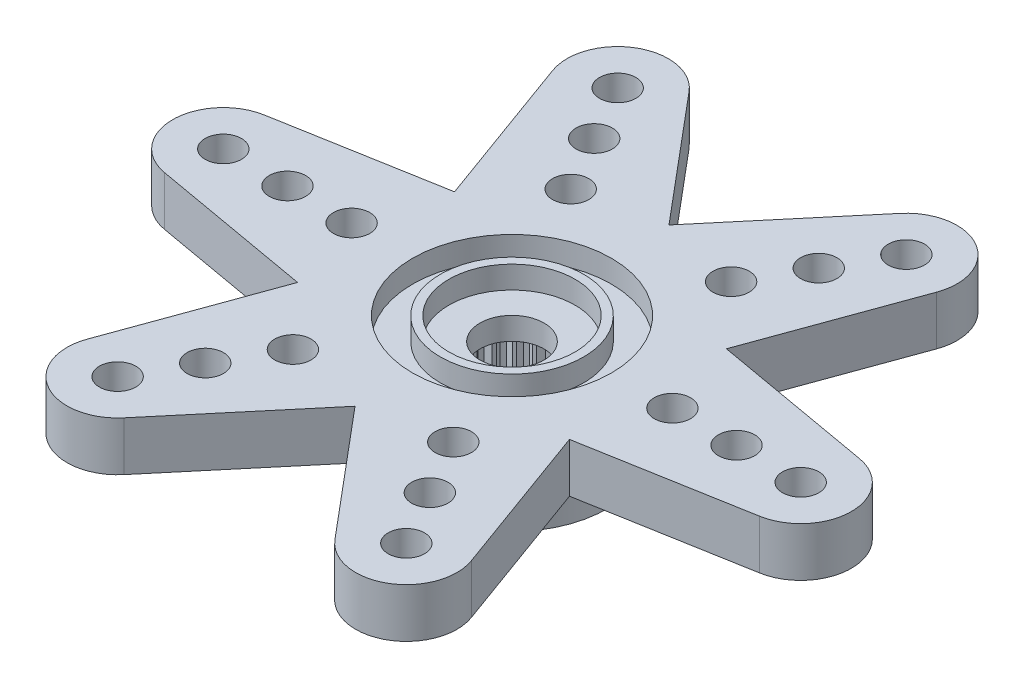
SolidWorks part; units mm, degrees
material "PA Type 6"
ref_plane "Plan de face" through (0, 0, 0) normal (0, 0, 1) x (1, 0, 0)
ref_plane "Plan de dessus" through (0, 0, 0) normal (0, 1, 0) x (1, 0, 0)
ref_plane "Plan de droite" through (0, 0, 0) normal (1, 0, 0) x (0, 0, -1)
ref_axis "Axe1" through (0, 0, 0) along (0, 1, 0)
sketch "Esquisse1" plane through (0, 0, 0) normal (0, 1, 0) x (1, 0, 0)
  line L0 (-15.87, 0) -> (15.87, 0) construction
  line L1 (0, 0) -> (0, -8.9896) construction
  line L4 (0, 0) -> (-6.3566, 3.67) construction
  line L11 (-13.9127, 2.3338) -> (-6.3566, 3.67)
  line L12 (-13.9127, -2.3338) -> (-6.3566, -3.67)
  line L13 (-6.3566, 3.67) -> (0, 3.67)
  line L14 (-6.3566, -3.67) -> (0, -3.67)
  circle A0 centre (0, 0) radius 15.87 construction
  arc A1 (-13.9127, 2.3338) -> (-13.9127, -2.3338) centre (-13.5, 0) ccw
  circle A4 centre (-13.5, 0) radius 0.85
  circle A5 centre (-10.5, 0) radius 0.85
  circle A6 centre (-7.5, 0) radius 0.85
  circle A12 centre (0, 0) radius 4.65
  circle A13 centre (0, 0) radius 1.5
  circle A14 centre (0, 0) radius 3.35
  circle A15 centre (0, 0) radius 2.95
  dimension "D1" = 31.74
  dimension "D2" = 1.7
  dimension "D3" = 27
  dimension "D9" = 9.3
  dimension "D10" = 6.7
  dimension "D11" = 0.4
  dimension "D12" = 3
  dimension "D5" = 7.34
  dimension "D4" = 3
  dimension "D6" = 3
  dimension "D13" = 30
sketch "Esquisse2" plane through (0, 0, 0) normal (0, 0, 1) x (1, 0, 0)
  line L0 (0, 3.9296) -> (0, -5.2174) construction
  line L1 (21.01, 0) -> (-21.01, 0) construction
  line L2 (0, -3.5) -> (-4.45, -3.5)
  line L3 (0, -3.5) -> (0, 2.1)
  line L4 (0, 2.1) -> (-4.45, 2.1)
  line L5 (-4.45, -3.5) -> (-4.45, 2.1)
  point P9 (-4.45, -0.2)
  dimension "D1" = 8.9
  dimension "D2" = 3.5
  dimension "D3" = 3.3
  dimension "D4" = 2.3
revolve "Révolution1" add sketch "Esquisse2" angle 360 about L0
sketch "Esquisse3" plane through (0, 2.1, 0) normal (0, 1, 0) x (1, 0, 0)
  line L2 (-6.3566, 3.67) -> (0, 3.67) construction
  line L3 (-13.9127, 2.3338) -> (-6.3566, 3.67) construction
  line L4 (0, 0) -> (0, -8.9896) construction
  line L5 (0, 0) -> (0, -8.9896) construction
  line L9 (-6.3566, -3.67) -> (0, -3.67) construction
  line L10 (-13.9127, -2.3338) -> (-6.3566, -3.67) construction
  line L11 (-6.3566, 3.67) -> (0, 3.67)
  line L15 (-13.9127, 2.3338) -> (-6.3566, 3.67)
  line L16 (-6.3566, -3.67) -> (0, -3.67)
  line L17 (-13.9127, -2.3338) -> (-6.3566, -3.67)
  line L18 (0, 3.67) -> (0, -3.67)
  circle A2 centre (-13.5, 0) radius 0.85 construction
  circle A3 centre (-10.5, 0) radius 0.85 construction
  circle A4 centre (-7.5, 0) radius 0.85 construction
  arc A6 (-13.9127, 2.3338) -> (-13.9127, -2.3338) centre (-13.5, 0) ccw construction
  circle A8 centre (-13.5, 0) radius 0.85
  circle A9 centre (-10.5, 0) radius 0.85
  circle A10 centre (-7.5, 0) radius 0.85
  arc A12 (-13.9127, 2.3338) -> (-13.9127, -2.3338) centre (-13.5, 0) ccw
extrude "Boss.-Extru.1" add sketch "Esquisse3" against normal up to vertex (2.3 mm away) up to point (-4.45, -0.2, 0)
pattern_circular "Répétition circulaire2" count 6 over 360 about axis through (0, 0, 0) along (0, 1, 0) of "Boss.-Extru.1"
sketch "Esquisse4" plane through (0, 2.1, 0) normal (0, 1, 0) x (1, 0, 0)
  circle A0 centre (0, 0) radius 2.95 construction
  circle A1 centre (0, 0) radius 2.95
extrude "Enlèv. mat.-Extru.1" cut sketch "Esquisse4" against normal blind 1.05
sketch "Esquisse5" plane through (0, 2.1, 0) normal (0, 1, 0) x (1, 0, 0)
  circle A0 centre (0, 0) radius 3.35 construction
  circle A1 centre (0, 0) radius 4.65 construction
  circle A2 centre (0, 0) radius 3.35
  circle A3 centre (0, 0) radius 4.65
extrude "Enlèv. mat.-Extru.2" cut sketch "Esquisse5" against normal blind 1.05
sketch "Esquisse6" plane through (0, -3.5, 0) normal (0, -1, 0) x (1, 0, 0)
  circle A0 centre (0, 0) radius 1.5 construction
  circle A1 centre (0, 0) radius 1.5
extrude "Enlèv. mat.-Extru.3" cut sketch "Esquisse6" against normal through all
sketch "Esquisse7" plane through (0, 0, 0) normal (0, 1, 0) x (1, 0, 0)
  line L6 (0.1267, -2.9973) -> (0.2711, -2.6537)
  line L7 (0.3973, -2.6377) -> (0.6227, -2.9347)
  line L8 (0, 0) -> (0, -3.7146) construction
  line L9 (0, 0) -> (0.3388, -2.6821) construction
  arc A4 (0.1267, -2.9973) -> (0.6227, -2.9347) centre (0, 0) ccw
  arc A5 (0.3973, -2.6377) -> (0.2711, -2.6537) centre (0.3388, -2.6821) ccw
  dimension "D2" = 6
  dimension "D7" = 0.37
  dimension "D4" = 0.5
  dimension "D5" = 7.2
  dimension "D6" = 60
sketch "Esquisse8" plane through (0, 0, 0) normal (0, 1, 0) x (1, 0, 0)
  circle A0 centre (0, 0) radius 2.68
  arc A1 (0.3973, -2.6377) -> (0.2711, -2.6537) centre (0.3388, -2.6821) ccw construction
  dimension "D1" = 0.05
extrude "Enlèv. mat.-Extru.4" cut sketch "Esquisse8" against normal through all
sketch "Esquisse9" plane through (0, 0, 0) normal (0, 1, 0) x (1, 0, 0)
  line L0 (0.1267, -2.9973) -> (0.2711, -2.6537) construction
  line L2 (0.1053, -3.0482) -> (0.2656, -2.6668)
  line L3 (-0.2656, -2.6668) -> (-0.1053, -3.0482)
  line L4 (0, -2.4923) -> (0, -2.738) construction
  line L5 (0, 0) -> (0, -3.7146) construction
  arc A0 (-0.1053, -3.0482) -> (0.1053, -3.0482) centre (0, 0) ccw
  circle A1 centre (0, 0) radius 2.68
  arc A2 (-0.2656, -2.6668) -> (0.2656, -2.6668) centre (0, 0) ccw
  arc A3 (0.1267, -2.9973) -> (0.6227, -2.9347) centre (0, 0) ccw construction
  dimension "D2" = 0.05
  dimension "D1" = 0
extrude "Enlèv. mat.-Extru.5" cut sketch "Esquisse9" against normal through all
pattern_circular "Répétition circulaire1" count 25 over 360 about axis through (0, 0, 0) along (0, 1, 0) of "Enlèv. mat.-Extru.5"
